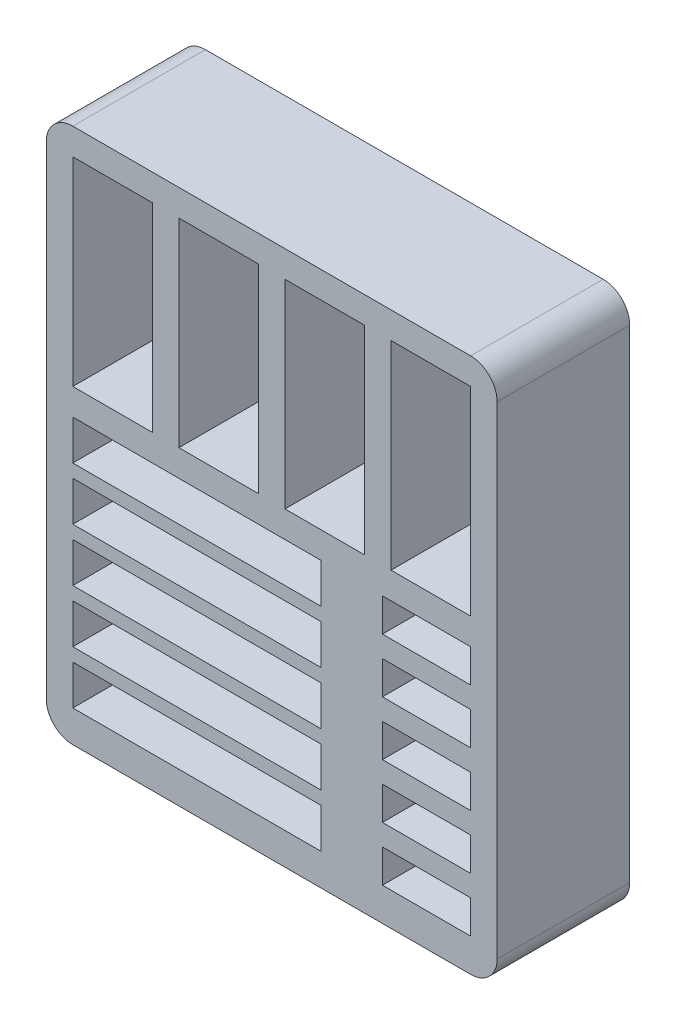
SolidWorks part; units mm, degrees
note: The reader was unsure of these and kept them because the rebuilt part matched: shared geometry of "Sketch1<3>".
ref_plane "Ön Düzlem" through (0, 0, 0) normal (0, 0, 1) x (1, 0, 0)
ref_plane "Üst Düzlem" through (0, 0, 0) normal (0, 1, 0) x (1, 0, 0)
ref_plane "Sağ Düzlem" through (0, 0, 0) normal (1, 0, 0) x (0, 0, -1)
sketch "Sketch1" plane through (0, 0, 0) normal (0, 0, 1) x (1, 0, 0)
  line L0 (18, 127.4998) -> (18, 6.9577) construction
  line L1 (4, 0) -> (64, 0)
  line L2 (0, 4) -> (0, 76.8)
  line L3 (4, 80.8) -> (64, 80.8)
  line L4 (68, 4) -> (68, 76.8)
  line L5 (4, 46.8) -> (16, 46.8)
  line L6 (4, 46.8) -> (4, 76.8)
  line L7 (4, 76.8) -> (16, 76.8)
  line L8 (16, 46.8) -> (16, 76.8)
  line L9 (32, 46.8) -> (20, 46.8)
  line L10 (32, 76.8) -> (20, 76.8)
  line L11 (20, 46.8) -> (20, 76.8)
  line L12 (32, 46.8) -> (32, 76.8)
  line L13 (34, 127.4998) -> (34, 21.0411) construction
  line L14 (4, 76.8) -> (16, 76.8)
  line L15 (16, 46.8) -> (16, 76.8)
  line L16 (4, 46.8) -> (4, 76.8)
  line L17 (4, 46.8) -> (16, 46.8)
  line L18 (32, 46.8) -> (20, 46.8)
  line L19 (20, 46.8) -> (20, 76.8)
  line L20 (32, 46.8) -> (32, 76.8)
  line L21 (32, 76.8) -> (20, 76.8)
  line L22 (36, 46.8) -> (36, 76.8)
  line L23 (36, 46.8) -> (48, 46.8)
  line L24 (48, 46.8) -> (48, 76.8)
  line L25 (64, 46.8) -> (52, 46.8)
  line L26 (52, 46.8) -> (52, 76.8)
  line L27 (50, 127.4998) -> (50, 6.9577) construction
  line L28 (36, 76.8) -> (48, 76.8)
  line L29 (64, 76.8) -> (52, 76.8)
  line L30 (64, 46.8) -> (64, 76.8)
  line L31 (4, 34.8) -> (41.4, 34.8)
  line L32 (45.9294, 11.6) -> (64, 11.6) construction
  line L33 (4, 42.8) -> (41.4, 42.8)
  line L34 (4, 42.8) -> (4, 36.8)
  line L35 (4, 36.8) -> (41.4, 36.8)
  line L36 (41.4, 42.8) -> (41.4, 36.8)
  line L37 (50.7, 5) -> (64, 5)
  line L38 (64, 10) -> (64, 5)
  line L39 (50.7, 10) -> (64, 10)
  line L40 (50.7, 10) -> (50.7, 5)
  line L41 (4, 34.8) -> (4, 28.8)
  line L42 (4, 28.8) -> (41.4, 28.8)
  line L43 (41.4, 34.8) -> (41.4, 28.8)
  line L44 (18, 119.4998) -> (18, -1.0423) construction
  line L45 (34, 119.4998) -> (34, 13.0411) construction
  line L46 (4, 26.8) -> (41.4, 26.8)
  line L47 (4, 26.8) -> (4, 20.8)
  line L48 (50.7, 29.6) -> (50.7, 34.6)
  line L49 (50.7, 37.8) -> (50.7, 42.8)
  line L50 (50.7, 37.8) -> (64, 37.8)
  line L51 (64, 37.8) -> (64, 42.8)
  line L52 (50.7, 42.8) -> (64, 42.8)
  line L53 (50.7, 29.6) -> (64, 29.6)
  line L54 (64, 29.6) -> (64, 34.6)
  line L55 (50.7, 34.6) -> (64, 34.6)
  line L56 (50.7, 21.4) -> (50.7, 26.4)
  line L57 (50.7, 21.4) -> (64, 21.4)
  line L58 (64, 21.4) -> (64, 26.4)
  line L59 (50.7, 26.4) -> (64, 26.4)
  line L60 (50.7, 13.2) -> (50.7, 18.2)
  line L61 (50.7, 13.2) -> (64, 13.2)
  line L62 (64, 13.2) -> (64, 18.2)
  line L63 (50.7, 18.2) -> (64, 18.2)
  line L64 (4, 20.8) -> (41.4, 20.8)
  line L65 (41.4, 26.8) -> (41.4, 20.8)
  line L66 (18, 111.4998) -> (18, -9.0423) construction
  line L67 (34, 111.4998) -> (34, 5.0411) construction
  line L68 (4, 18.8) -> (41.4, 18.8)
  line L69 (4, 18.8) -> (4, 12.8)
  line L70 (4, 12.8) -> (41.4, 12.8)
  line L71 (41.4, 18.8) -> (41.4, 12.8)
  line L72 (18, 103.4998) -> (18, -17.0423) construction
  line L73 (34, 103.4998) -> (34, -2.9589) construction
  line L74 (4, 10.8) -> (41.4, 10.8)
  line L75 (4, 10.8) -> (4, 4.8)
  line L76 (4, 4.8) -> (41.4, 4.8)
  line L77 (41.4, 10.8) -> (41.4, 4.8)
  line L78 (18, 95.4998) -> (18, -25.0423) construction
  line L79 (34, 95.4998) -> (34, -10.9589) construction
  line L100 (50.7, -39.8) -> (64, -39.8) [skipped]
  line L101 (50.7, -39.8) -> (50.7, -34.8) [skipped]
  line L102 (64, -39.8) -> (64, -34.8) [skipped]
  line L103 (50.7, -34.8) -> (64, -34.8) [skipped]
  line L104 (50.7, -52.7333) -> (64, -52.7333) [skipped]
  line L105 (50.7, -52.7333) -> (50.7, -47.7333) [skipped]
  line L106 (64, -52.7333) -> (64, -47.7333) [skipped]
  line L107 (50.7, -47.7333) -> (64, -47.7333) [skipped]
  line L108 (50.7, -26.8667) -> (64, -26.8667) [skipped]
  line L109 (50.7, -26.8667) -> (50.7, -21.8667) [skipped]
  line L110 (64, -26.8667) -> (64, -21.8667) [skipped]
  line L111 (50.7, -21.8667) -> (64, -21.8667) [skipped]
  line L112 (50.7, 24.8667) -> (64, 24.8667) [skipped]
  line L113 (50.7, 24.8667) -> (50.7, 29.8667) [skipped]
  line L114 (64, 24.8667) -> (64, 29.8667) [skipped]
  line L115 (50.7, 29.8667) -> (64, 29.8667) [skipped]
  line L116 (50.7, 11.9333) -> (64, 11.9333) [skipped]
  line L117 (50.7, 11.9333) -> (50.7, 16.9333) [skipped]
  line L118 (64, 11.9333) -> (64, 16.9333) [skipped]
  line L119 (50.7, 16.9333) -> (64, 16.9333) [skipped]
  line L120 (50.7, -1) -> (64, -1) [skipped]
  line L121 (50.7, -1) -> (50.7, 4) [skipped]
  line L122 (64, -1) -> (64, 4) [skipped]
  line L123 (50.7, 4) -> (64, 4) [skipped]
  line L124 (50.7, -13.9333) -> (64, -13.9333) [skipped]
  line L125 (50.7, -13.9333) -> (50.7, -8.9333) [skipped]
  line L126 (64, -13.9333) -> (64, -8.9333) [skipped]
  line L127 (50.7, -8.9333) -> (64, -8.9333) [skipped]
  arc A0 (64, 80.8) -> (68, 76.8) centre (64, 76.8) cw
  arc A1 (64, 0) -> (68, 4) centre (64, 4) ccw
  arc A2 (4, 0) -> (0, 4) centre (4, 4) cw
  arc A3 (0, 76.8) -> (4, 80.8) centre (4, 76.8) cw
  point P56 (0, 0)
  dimension "D19" = 4
  dimension "D1" = 4
  dimension "D2" = 80.8
  dimension "D3" = 4
  dimension "D4" = 2
  dimension "D5" = 2
  dimension "D6" = 12
  dimension "D7" = 4
  dimension "D8" = 6
  dimension "D9" = 4
  dimension "D10" = 37.4
  dimension "D11" = 1.6
  dimension "D12" = 30
  dimension "D13" = 5
  dimension "D15" = 13.3
  dimension "D16" = 5
  dimension "D18" = 5
extrude "Boss-Extrude1" add sketch "Sketch1" along normal blind 2 contours L3 A0 L4 A1 L1 A2 L2 A3
extrude "Boss-Extrude2" add sketch "Sketch1<3>" along normal blind 20
sketch "Sketch1<3>" plane through (0, 0, 0) normal (0, 0, 1) x (1, 0, 0) same geometry as "Sketch1"
